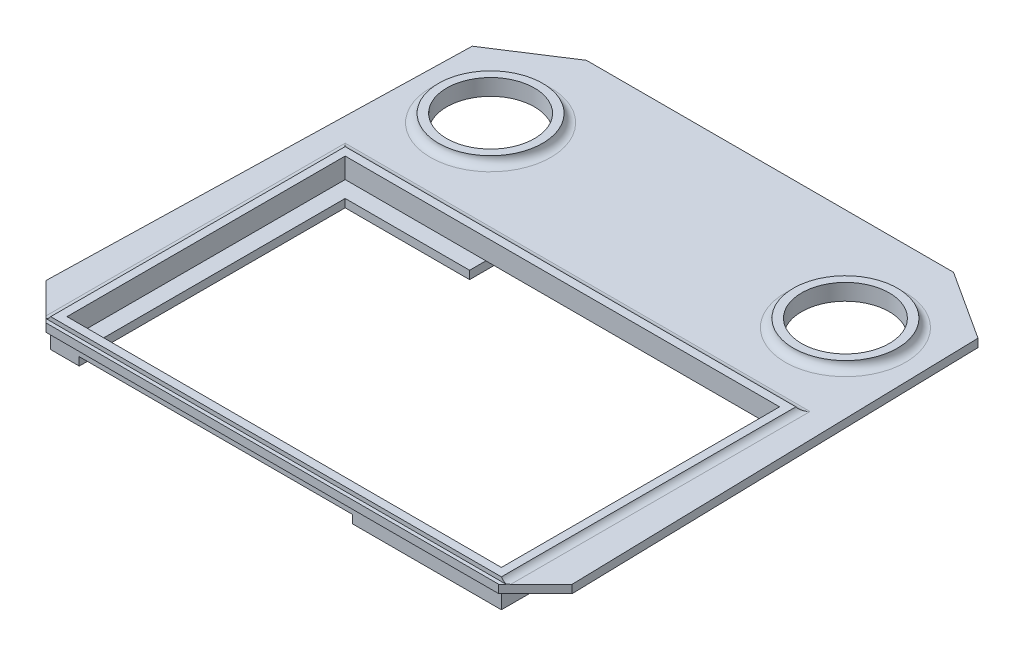
SolidWorks part; units mm, degrees
ref_plane "Front Plane" through (0, 0, 0) normal (0, 0, 1) x (1, 0, 0)
ref_plane "Top Plane" through (0, 0, 0) normal (0, 1, 0) x (1, 0, 0)
ref_plane "Right Plane" through (0, 0, 0) normal (1, 0, 0) x (0, 0, -1)
ref_axis "X Axis" through (-109.587, 0, 0) along (1, 0, 0)
ref_axis "Y Axis" through (0, 0, -140.1599) along (0, 0, 1)
ref_axis "Z Axis" through (0, 50.6832, 0) along (0, -1, 0)
ref_plane "LCD Plane" through (0, 24, 0) normal (0, 1, 0) x (1, 0, 0)
sketch "Sketch1" plane through (0, 24, 0) normal (0, 1, 0) x (1, 0, 0)
  line L0 (-55.25, 36.1) -> (55.25, 36.1)
  line L1 (-53.25, -34.1) -> (53.25, -34.1)
  line L2 (-53.25, -34.1) -> (-53.25, 34.1)
  line L3 (-53.25, 34.1) -> (53.25, 34.1)
  line L4 (53.25, -34.1) -> (53.25, 34.1)
  line L5 (-53.25, -34.1) -> (53.25, 34.1) construction
  line L6 (-53.25, 34.1) -> (53.25, -34.1) construction
  line L7 (55.25, -36.1) -> (55.25, 36.1)
  line L8 (-55.25, -36.1) -> (55.25, -36.1)
  line L9 (-55.25, -36.1) -> (-55.25, 36.1)
  point P0 (0, 0)
  point P3 (0, 0)
  dimension "D1" = 106.5
  dimension "D2" = 68.2
  dimension "D3" = 2
extrude "Boss-Extrude1" add sketch "Sketch1" along normal blind 5
sketch "Sketch2" plane through (0, 24, 0) normal (0, 1, 0) x (1, 0, 0)
  line L0 (-55.25, 36.1) -> (-55.25, -36.1)
  line L1 (-55.25, -36.1) -> (-48.25, -36.1)
  line L2 (55.25, -36.1) -> (55.25, 36.1)
  line L3 (55.25, 36.1) -> (48.25, 36.1)
  line L4 (-53.25, 34.1) -> (-53.25, -34.1) construction
  line L5 (-53.25, -34.1) -> (53.25, -34.1) construction
  line L6 (53.25, -34.1) -> (53.25, 34.1) construction
  line L7 (53.25, 34.1) -> (-53.25, 34.1) construction
  line L8 (-49.25, 30.1) -> (-49.25, -30.1)
  line L10 (49.25, -30.1) -> (49.25, 30.1)
  line L12 (-49.25, -30.1) -> (49.25, -30.1) construction
  line L13 (49.25, 30.1) -> (-49.25, 30.1) construction
  line L14 (-49.25, 30.1) -> (-18.75, 30.1)
  line L15 (-18.75, 30.1) -> (-18.75, 36.1)
  line L16 (49.25, 30.1) -> (48.25, 30.1)
  line L17 (48.25, 30.1) -> (48.25, 36.1)
  line L18 (-18.75, 36.1) -> (-55.25, 36.1)
  line L19 (-49.25, -30.1) -> (-48.25, -30.1)
  line L21 (49.25, -30.1) -> (18.75, -30.1)
  line L23 (-55.25, -36.1) -> (55.25, -36.1) construction
  line L24 (-48.25, -30.1) -> (-48.25, -36.1)
  line L25 (-53.25, -34.1) -> (53.25, -34.1) construction
  line L26 (18.75, -36.1) -> (55.25, -36.1)
  line L27 (-18.75, 30.1) -> (48.25, 30.1) construction
  line L28 (-48.25, -30.1) -> (18.75, -30.1) construction
  line L29 (18.75, -30.1) -> (18.75, -36.1)
  dimension "D1" = 4
  dimension "D2" = 67
  dimension "D3" = 1
extrude "Boss-Extrude2" add sketch "Sketch2" against normal blind 2
ref_plane "Stick Plane" through (0, 28, 0) normal (0, 1, 0) x (1, 0, 0)
sketch "Sketch4" plane through (0, 28, 0) normal (0, 1, 0) x (1, 0, 0)
  line L0 (0, 0) -> (0, 102.87) construction
  line L2 (-43.5, 60) -> (43.5, 60) construction
  circle A0 centre (-43.5, 60) radius 10.75
  circle A1 centre (43.5, 60) radius 10.75
  circle A2 centre (-43.5, 60) radius 12.75
  circle A3 centre (43.5, 60) radius 12.75
  point P4 (0, 60)
  point P6 (0, 0)
  dimension "D3" = 21.5
  dimension "D1" = 60
  dimension "D2" = 87
  dimension "D4" = 2
extrude "Boss-Extrude3" add sketch "Sketch4" along normal blind 2 separate body
sketch "Sketch5" plane through (0, 28, 0) normal (0, 1, 0) x (1, 0, 0)
  line L0 (-64.5, -28) -> (-62, 74)
  line L5 (-62, 74) -> (-45, 85)
  line L6 (-45, 85) -> (45, 85)
  line L7 (45, 85) -> (62, 74)
  line L8 (62, 74) -> (64.5, -28)
  line L9 (64.5, -28) -> (55.5, -37)
  line L10 (55.5, -37) -> (-55.5, -37)
  line L11 (-55.5, -37) -> (-64.5, -28)
  line L12 (0, 0) -> (0, -37) construction
  line L13 (0, 0) -> (0, 85) construction
  line L14 (-62, 74) -> (62, 74) construction
  line L15 (-64.5, -28) -> (64.5, -28) construction
  line L16 (-53.25, 34.1) -> (-53.25, -34.1)
  line L17 (-53.25, -34.1) -> (53.25, -34.1)
  line L18 (53.25, -34.1) -> (53.25, 34.1)
  line L19 (53.25, 34.1) -> (-53.25, 34.1)
  circle A0 centre (-43.5, 60) radius 10.75
  circle A1 centre (43.5, 60) radius 10.75
  dimension "D1" = 37
  dimension "D2" = 85
  dimension "D3" = 124
  dimension "D4" = 129
  dimension "D5" = 9
  dimension "D6" = 11
  dimension "D7" = 111
  dimension "D8" = 90
extrude "Boss-Extrude4" add sketch "Sketch5" against normal blind 2
fillet "Fillet2" radius 2 5 edges at (43.5, 28, -47.25) (-43.5, 28, -47.25) (55.25, 28, 0) (0, 28, -36.1) (-55.25, 28, 0)
